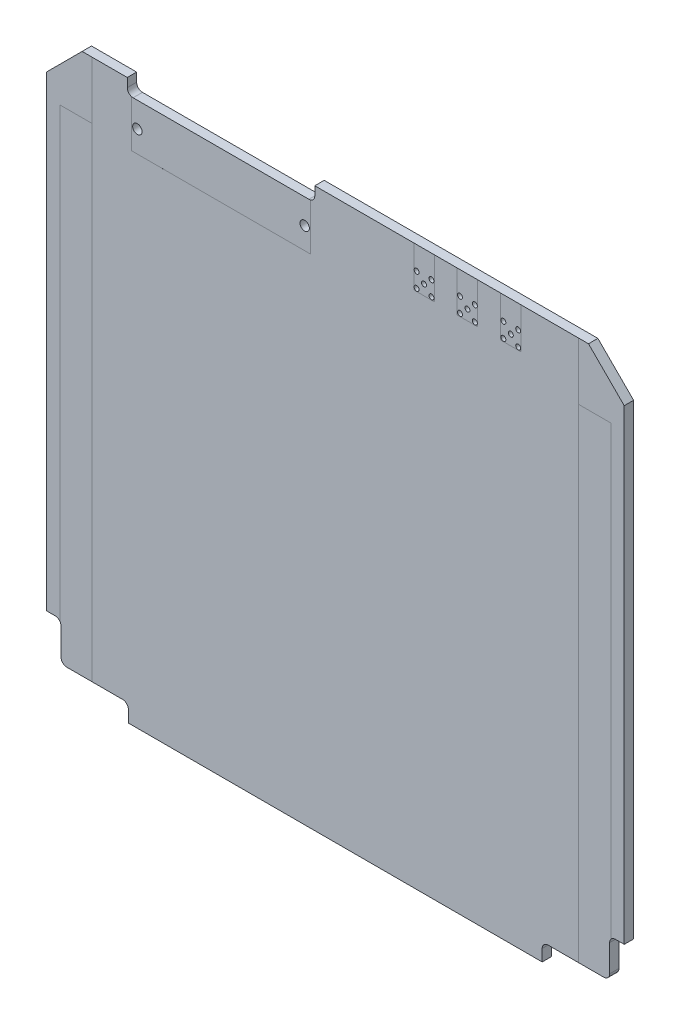
SolidWorks part; units mm, degrees
material "Oshpark board"
ref_plane "Front Plane" through (0, 0, 0) normal (0, 0, 1) x (1, 0, 0)
ref_plane "Top Plane" through (0, 0, 0) normal (0, 1, 0) x (1, 0, 0)
ref_plane "Right Plane" through (0, 0, 0) normal (1, 0, 0) x (0, 0, -1)
ref_plane "Plane4" through (0, 0, -0.0125) normal (0, 0, -1) x (-1, 0, 0)
sketch "Sketch1" plane through (0, 0, -0.0125) normal (0, 0, -1) x (-1, 0, 0)
  line L0 (35.3, -50) -> (35.3, -48)
  line L1 (36.3, -47) -> (45.8, -47)
  line L2 (46.8, -46) -> (46.8, -41.4)
  line L3 (47.8, -40.4) -> (49.3, -40.4)
  line L4 (49.3, -40.4) -> (49.3, 39.2)
  line L5 (49.3, 39.2) -> (43.2, 45.3)
  line L6 (43.2, 45.3) -> (35.5, 45.3)
  line L7 (35.5, 45.3) -> (35.5, 43.8)
  line L8 (34.5, 42.8) -> (4.5, 42.8)
  line L9 (3.5, 43.8) -> (3.5, 45.3)
  line L10 (3.5, 45.3) -> (-43.2, 45.3)
  line L11 (-43.2, 45.3) -> (-49.3, 39.2)
  line L12 (-49.3, 39.2) -> (-49.3, -40.4)
  line L13 (-49.3, -40.4) -> (-47.8, -40.4)
  line L14 (-46.8, -41.4) -> (-46.8, -46)
  line L15 (-45.8, -47) -> (-36.3, -47)
  line L16 (-35.3, -48) -> (-35.3, -50)
  line L17 (-35.3, -50) -> (35.3, -50)
  line L18 (0, -50) -> (0, 45.3) construction
  line L19 (19.5, 42.8) -> (19.5, 25.5258) construction
  line L20 (-13.87, 41.37) -> (-16.41, 38.83) construction
  line L21 (-21.27, 41.37) -> (-23.81, 38.83) construction
  line L22 (-28.67, 41.37) -> (-31.21, 38.83) construction
  arc A0 (35.3, -48) -> (36.3, -47) centre (36.3, -48) cw
  arc A1 (45.8, -47) -> (46.8, -46) centre (45.8, -46) ccw
  arc A2 (46.8, -41.4) -> (47.8, -40.4) centre (47.8, -41.4) cw
  arc A3 (35.5, 43.8) -> (34.5, 42.8) centre (34.5, 43.8) cw
  arc A4 (4.5, 42.8) -> (3.5, 43.8) centre (4.5, 43.8) cw
  arc A5 (-47.8, -40.4) -> (-46.8, -41.4) centre (-47.8, -41.4) cw
  arc A6 (-46.8, -46) -> (-45.8, -47) centre (-45.8, -46) ccw
  arc A7 (-36.3, -47) -> (-35.3, -48) centre (-36.3, -48) cw
  circle A8 centre (-21.27, 41.37) radius 0.425
  circle A9 centre (-23.81, 41.37) radius 0.425
  circle A10 centre (-22.54, 40.1) radius 0.425
  circle A11 centre (-13.87, 41.37) radius 0.425
  circle A12 centre (-23.81, 38.83) radius 0.425
  circle A13 centre (-16.41, 41.37) radius 0.425
  circle A14 centre (-15.14, 40.1) radius 0.425
  circle A15 centre (-21.27, 38.83) radius 0.425
  circle A16 centre (-28.67, 41.37) radius 0.425
  circle A17 centre (-31.21, 41.37) radius 0.425
  circle A18 centre (-16.41, 38.83) radius 0.425
  circle A19 centre (-29.94, 40.1) radius 0.425
  circle A20 centre (-31.21, 38.83) radius 0.425
  circle A21 centre (-28.67, 38.83) radius 0.425
  circle A22 centre (33.775, 38.54) radius 0.8
  circle A23 centre (5.225, 38.54) radius 0.8
  circle A24 centre (-13.87, 38.83) radius 0.425
  point P35 (-15.14, 40.1)
  dimension "D7" = 2.5
  dimension "D8" = 1.6
  dimension "D9" = 14.275
  dimension "D10" = 4.26
  dimension "D11" = 1
  dimension "D12" = 1
  dimension "D13" = 1
  dimension "D14" = 1
  dimension "D15" = 1
  dimension "D16" = 1
  dimension "D17" = 1
  dimension "D18" = 1
  dimension "D26" = 0.85
  dimension "D1" = 98.6
  dimension "D2" = 95.3
  dimension "D3" = 14
  dimension "D4" = 9.6
  dimension "D5" = 2.5
  dimension "D6" = 3
  dimension "D19" = 14
  dimension "D20" = 2.5
  dimension "D21" = 6.1
  dimension "D22" = 6.1
  dimension "D23" = 32
  dimension "D24" = 2.54
  dimension "D25" = 2.54
  dimension "D28" = 7.4
  dimension "D29" = 3.93
  dimension "D30" = 35.43
  dimension "D31" = 45
  dimension "D32" = 45
  dimension "D33" = 29.8
  dimension "D34" = 50
  dimension "D27" = 3
extrude "Boss-Extrude1" add sketch "Sketch1" against normal blind 1.6
sketch "thermalContacts_lower" plane through (0, 0, -0.0125) normal (0, 0, -1) x (-1, 0, 0)
  line L3 (47, 35.5) -> (47, -41.5)
  line L4 (41.5, 35.5) -> (41.5, 41.5)
  line L5 (41.5, 35.5) -> (47, 35.5)
  line L9 (-47, 35.5) -> (-47, -41.1726)
  line L10 (-41.5, 35.5) -> (-47, 35.5)
  line L11 (-41.5, 35.5) -> (-41.5, 42.5522)
  line L14 (-41.5, 42.5522) -> (-41.5, 47.8583)
  line L18 (41.5, 41.5) -> (41.5, 47)
  line L20 (47, -41.5) -> (59.8273, -41.5)
  line L21 (59.8273, -41.5) -> (59.8273, 47)
  line L22 (-54.1782, 47.8583) -> (-41.5, 47.8583)
  line L23 (41.5, 47) -> (59.8273, 47)
  line L24 (-54.1782, 47.8583) -> (-54.1782, -41.1726)
  line L25 (-47, -41.1726) -> (-54.1782, -41.1726)
  line L26 (43.2, 45.3) -> (35.5, 45.3) construction
  line L27 (49.3, -40.4) -> (49.3, 39.2) construction
  line L28 (3.5, 45.3) -> (-43.2, 45.3) construction
  line L29 (-49.3, 39.2) -> (-49.3, -40.4) construction
  dimension "D1" = 9.8
  dimension "D2" = 7.8
  dimension "D3" = 2.3
  dimension "D4" = 9.8
  dimension "D5" = 7.8
  dimension "D6" = 2.3
sketch "thermalContacts_upper" plane through (0, 0, 1.5875) normal (0, 0, 1) x (1, 0, 0)
  line L3 (-47, 35.5) -> (-47, -41.5)
  line L4 (-41.5, 35.5) -> (-41.5, 41.5)
  line L5 (-41.5, 35.5) -> (-47, 35.5)
  line L9 (47, 35.5) -> (47, -41.5)
  line L10 (41.5, 35.5) -> (47, 35.5)
  line L11 (41.5, 35.5) -> (41.5, 41.5)
  line L14 (41.5, 41.5) -> (41.5, 47)
  line L15 (41.5, 41.5) -> (49.5, 41.5) construction
  line L18 (-41.5, 41.5) -> (-41.5, 47)
  line L19 (-41.5, 41.5) -> (-49.5, 41.5) construction
  line L20 (47, -41.5) -> (59.8273, -41.5)
  line L21 (59.8273, -41.5) -> (59.8273, 47)
  line L22 (59.8273, 47) -> (41.5, 47)
  line L23 (-41.5, 47) -> (-56.1922, 47)
  line L24 (-56.1922, 47) -> (-56.1922, -41.5)
  line L25 (-56.1922, -41.5) -> (-47, -41.5)
extrude "keepOut_top" cut sketch "thermalContacts_lower" against normal blind 0.0001
extrude "keepOut_bottom" cut sketch "thermalContacts_upper" against normal blind 0.0001
sketch "partFootprints" plane through (0, 0, 1.5875) normal (0, 0, 1) x (1, 0, 0)
  line L0 (-34.74, 34.84) -> (-34.74, 42.8292)
  line L1 (-4.26, 34.84) -> (-34.74, 34.84)
  line L2 (-41.5, 45.3) -> (-35.5, 45.3) construction
  line L3 (-36.1132, 45.3) -> (-39.5054, 45.3) construction
  line L4 (-4.26, 34.84) -> (-4.26, 42.8292)
  line L5 (-49.3, -40.4) -> (-49.3, 39.2) construction
  line L6 (13.39, 45.3) -> (13.39, 38.35)
  line L7 (13.39, 38.35) -> (16.89, 38.35)
  line L8 (16.89, 38.35) -> (16.89, 45.3)
  line L9 (16.89, 45.3) -> (13.39, 45.3)
  line L10 (20.79, 45.3) -> (20.79, 38.35)
  line L11 (20.79, 38.35) -> (24.29, 38.35)
  line L12 (24.29, 38.35) -> (24.29, 45.3)
  line L13 (24.29, 45.3) -> (20.79, 45.3)
  line L14 (28.19, 45.3) -> (28.19, 38.35)
  line L15 (28.19, 38.35) -> (31.69, 38.35)
  line L16 (31.69, 38.35) -> (31.69, 45.3)
  line L17 (31.69, 45.3) -> (28.19, 45.3)
  line L18 (49.3, -40.4) -> (49.3, 39.2) construction
  line L20 (-34.74, 42.8292) -> (-4.26, 42.8292)
  line L21 (-3.5, 45.3) -> (41.5, 45.3) construction
  line L22 (14.12, 38.35) -> (15.8235, 38.35) construction
  line L25 (13.39, 42.2411) -> (13.39, 38.35) construction
  line L26 (16.89, 41.85) -> (16.89, 38.35) construction
  arc A0 (-35.5, 43.8) -> (-34.5, 42.8) centre (-34.5, 43.8) ccw construction
  arc A1 (-4.5, 42.8) -> (-3.5, 43.8) centre (-4.5, 43.8) ccw construction
  dimension "D1" = 10.46
  dimension "D2" = 14.56
  dimension "D3" = 30.48
  dimension "D4" = 6.95
  dimension "D5" = 17.61
  dimension "D7" = 7.4
  dimension "D8" = 3.5
  dimension "D6" = 3
extrude "footPrints" cut sketch "partFootprints" against normal blind 0.0001
sketch "Sketch3" plane through (0, 0, 1.5875) normal (0, 0, 1) x (1, 0, 0)
  line L0 (41.5, -41.5) -> (41.5, -36) construction
  line L1 (41.5, -47) -> (41.5, 35.5)
  line L2 (47, 35.5) -> (47, -40.8) construction
  line L3 (46.8, -41.4) -> (46.8, -46) construction
  line L4 (45.8, -47) -> (36.3, -47) construction
  line L5 (47, 35.5) -> (47, -40.8)
  line L6 (46.8, -41.4) -> (46.8, -46)
  line L7 (45.8, -47) -> (41.5, -47)
  line L8 (41.5, 35.5) -> (47, 35.5) construction
  line L9 (41.5, 35.5) -> (47, 35.5)
  line L10 (0, -50) -> (0, 45.3) construction
  line L11 (35.3, -50) -> (-35.3, -50) construction
  line L12 (-3.5, 45.3) -> (13.39, 45.3) construction
  line L13 (-41.5, 35.5) -> (-47, 35.5)
  line L14 (-45.8, -47) -> (-41.5, -47)
  line L15 (-46.8, -41.4) -> (-46.8, -46)
  line L16 (-47, 35.5) -> (-47, -40.8)
  line L17 (-41.5, -47) -> (-41.5, 35.5)
  arc A0 (47, -40.8) -> (46.8, -41.4) centre (47.8, -41.4) ccw construction
  arc A1 (45.8, -47) -> (46.8, -46) centre (45.8, -46) ccw construction
  arc A2 (47, -40.8) -> (46.8, -41.4) centre (47.8, -41.4) ccw
  arc A3 (45.8, -47) -> (46.8, -46) centre (45.8, -46) ccw
  arc A4 (-45.8, -47) -> (-46.8, -46) centre (-45.8, -46) cw
  arc A5 (-47, -40.8) -> (-46.8, -41.4) centre (-47.8, -41.4) cw
extrude "caution_top" cut sketch "Sketch3" against normal blind 0.0001
ref_plane "midplane_Z" through (0, 0, 0.7875) normal (0, 0, 1) x (1, 0, 0)
mirror "caution_bottom" about plane through (0, 0, 0.7875) normal (0, 0, 1) of "caution_top"
